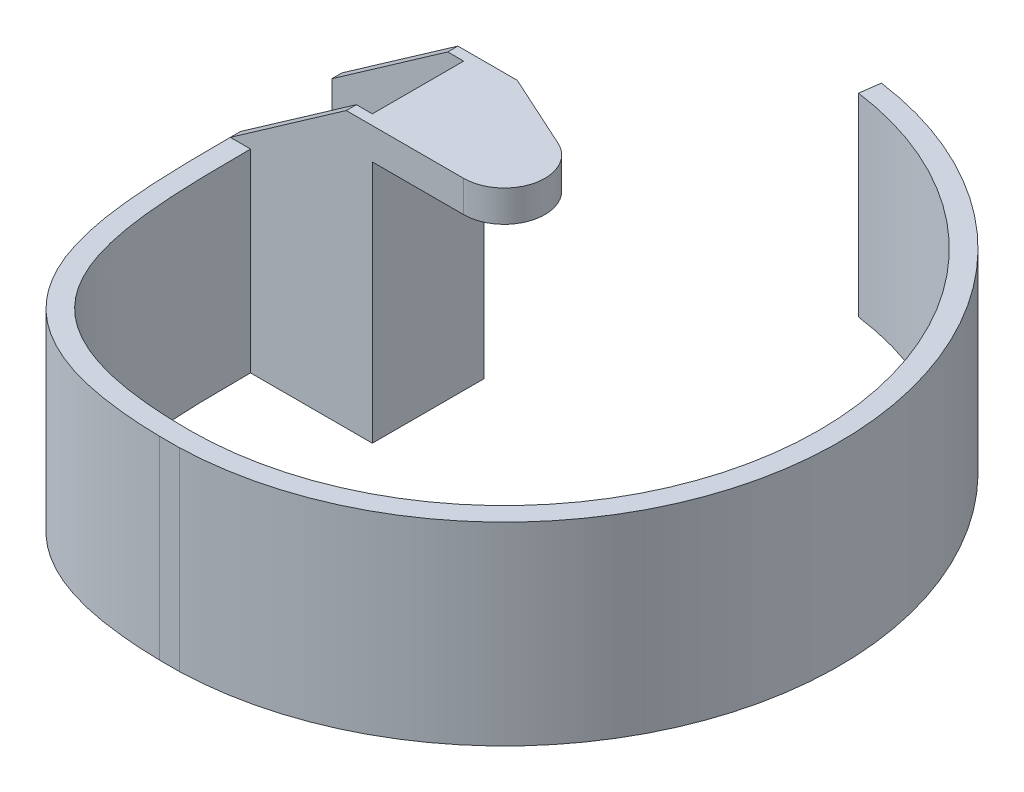
SolidWorks part; units mm, degrees
ref_plane "Front Plane" through (0, 0, 0) normal (0, 0, 1) x (1, 0, 0)
ref_plane "Top Plane" through (0, 0, 0) normal (0, 1, 0) x (1, 0, 0)
ref_plane "Right Plane" through (0, 0, 0) normal (1, 0, 0) x (0, 0, -1)
sketch "Agitator / Kick Alignment" plane through (0, 0, 0) normal (0, 1, 0) x (1, 0, 0)
  line L0 (-131.2224, 60.1613) -> (-110.3231, 213.6853) construction
  line L1 (5.6533, 41.527) -> (26.5533, 195.0509) construction
  line L2 (16.1033, 118.2889) -> (-271.78, 157.48) construction
  line L3 (-131.2224, 60.1613) -> (-110.3231, 213.6853)
  line L4 (5.6533, 41.527) -> (26.5533, 195.0509)
  line L5 (16.1033, 118.2889) -> (-271.78, 157.48)
sketch "Sketch3" plane through (0, 0, 0) normal (0, 1, 0) x (1, 0, 0)
  line L0 (5.6533, 41.527) -> (26.5533, 195.0509) construction
  line L1 (26.5533, 195.0509) -> (28.2664, 207.6348)
  line L2 (-133.35, -25.4) -> (0, -25.4)
  line L4 (-36.2865, 44.45) -> (-146.0084, 44.45)
  line L6 (-36.2865, 44.45) -> (10.5332, 23.113)
  line L7 (-6.3292, -209.4544) -> (6.3292, -209.4544)
  line L8 (128.5561, -196.85) -> (-132.7269, -196.85) construction
  line L9 (-146.0084, -25.4) -> (-146.0084, 44.45)
  line L10 (-133.35, -99.724) -> (-133.35, 83.6944) construction
  line L11 (-133.35, -25.4) -> (-133.35, 44.45)
  line L12 (-6.3292, -209.4544) -> (-6.3292, -209.4544)
  line L13 (-146.0084, -12.7416) -> (0, -12.7416) construction
  line L14 (-39.0349, 31.7916) -> (5.2839, 11.5944) construction
  line L15 (-39.0349, 31.7916) -> (-146.0084, 31.7916) construction
  line L16 (-133.35, -25.4) -> (-146.0084, -25.4)
  arc A0 (26.5533, 195.0509) -> (0, -196.85) centre (0, 0) cw
  arc A1 (28.2664, 207.6348) -> (6.3292, -209.4544) centre (0, 0) cw
  arc A4 (0, -25.4) -> (10.5332, 23.113) centre (0, 0) ccw
  arc A5 (0, -196.85) -> (-133.35, -25.4) centre (-91.3959, -130.3524) cw construction
  arc A6 (6.3292, -209.4544) -> (-138.0641, -13.6073) centre (-91.3959, -130.3524) cw construction
  arc A10 (-6.3292, -209.4544) -> (-6.3292, -209.4544) centre (-6.3292, -209.4544) cw
  arc A11 (-6.3292, -209.4544) -> (-6.3292, -209.4544) centre (-6.3292, -209.4544) ccw
  arc A12 (0, -12.7416) -> (5.2839, 11.5944) centre (0, 0) ccw construction
  spline S0 degree 1 poles (-146.0084, -12.7416) (-6.3292, -209.4544) knots 0 0 1 1 construction
  spline S1 degree 3 poles (-146.0084, -12.7416) (-146.0084, -14.4342) (-146.0083, -17.8078) (-146.0086, -21.6028) (-146.0083, -24.5474) (-146.0089, -27.9687) (-145.9928, -37.6758) (-145.8479, -52.8132) (-145.2521, -71.5713) (-144.0488, -89.4194) (-142.0319, -106.3622) (-137.955, -127.7287) (-131.2897, -147.2622) (-120.9286, -164.5766) (-111.1011, -176.2073) (-99.1376, -186.2307) (-85.0632, -194.4723) (-71.5911, -199.824) (-59.7326, -203.2181) (-50.2806, -205.3279) (-40.2501, -207.0086) (-31.3897, -208.0563) (-23.9871, -208.6846) (-18.276, -209.0513) (-13.3774, -209.2699) (-9.3819, -209.3926) (-7.3435, -209.4368) (-6.3292, -209.4544) knots -0.039869 -0.039869 -0.039869 -0.039869 -0.023876 -0.007997 -0.003998 0.003998 0.024105 0.088079 0.152052 0.216026 0.28 0.343974 0.471922 0.535895 0.599869 0.663843 0.727817 0.791791 0.823778 0.855765 0.887751 0.919738 0.935732 0.951725 0.967719 0.975715 0.983712 0.983712 0.983712 0.983712 only from (-146.0084, -25.4) to (-6.3292, -209.4544)
  spline S3 degree 3 poles (-133.35, -25.4) (-133.35, -131.2333) (-127, -196.85) (0, -196.85) knots 0 0 0 0 1 1 1 1
  point P22 (0, -209.4544)
  dimension "D1" = 196.85
  dimension "D6" = 25.4
  dimension "D9" = 317.5
  dimension "D10" = 381
  dimension "D3" = 12.7
  dimension "D4" = 69.85
  dimension "D7" = 24.5
  dimension "D8" = 133.35
extrude "Base extrude" add sketch "Sketch3" along normal blind 121.285 contours S3 L2 A4 L6 L4 L9 S1 L7 A1 L1 A0 region at (32.8405, 0, -200.6035)
extrude "Motor box & Core support" add sketch "Sketch3<4>" along normal offset from surface (172.085 mm away) 50.8 contours L16 L11 L4 L9 | L2 A4 L6 L4 L11 region at (-60.4233, 0, -7.6989) region at (-139.6792, 0, -9.525) up to face at (2.0047, 121.285, 15.5178) offset beyond the face yes
sketch "Sketch3<4>" plane through (0, 0, 0) normal (0, 1, 0) x (1, 0, 0) same geometry as "Sketch3"
sketch "Sketch4" plane through (0, 0, 25.4) normal (0, 0, 1) x (1, 0, 0)
  line L0 (25.4, 0) -> (25.4, 172.085) construction
  line L1 (25.4, 0) -> (-57.15, 0)
  line L2 (25.4, 0) -> (25.4, 152.4)
  line L3 (25.4, 152.4) -> (-57.15, 152.4)
  line L4 (-57.15, 0) -> (-57.15, 152.4)
  dimension "D1" = 152.4
  dimension "D2" = 82.55
extrude "Wheel space" cut sketch "Sketch4" against normal up to next
sketch "Sketch5" plane through (0, 172.085, 0) normal (0, 1, 0) x (1, 0, 0)
  line L0 (-146.0084, -25.4) -> (-146.0084, 44.45) construction
  line L7 (-63.5, 44.45) -> (-63.5, -25.4)
  line L8 (-63.5, 38.1) -> (-63.5, -19.05)
  line L18 (-146.0084, 38.1) -> (-146.0084, -19.05)
  line L22 (-139.6584, -19.05) -> (0, -19.05)
  line L23 (7.8999, 17.3348) -> (-37.6652, 38.1)
  line L24 (-37.6652, 38.1) -> (-139.6584, 38.1)
  line L25 (-139.6584, 38.1) -> (-139.6584, -19.05)
  line L26 (-146.0084, -19.05) -> (-63.5, -19.05)
  line L28 (-63.5, 38.1) -> (-146.0084, 38.1)
  arc A4 (0, -19.05) -> (7.8999, 17.3348) centre (0, 0) ccw
  dimension "D1" = 6.35
  dimension "D2" = 6.35
extrude "Motor space" cut sketch "Sketch5" against normal offset from surface (121.285 mm away) 50.8 up to face at (-24.6276, 0, 4.5125)
sketch "Sketch6" plane through (0, 0, 25.4) normal (0, 0, 1) x (1, 0, 0)
  line L0 (-146.0084, 121.285) -> (-73.4585, 172.085)
  line L1 (0, 172.085) -> (-146.0084, 172.085) construction
  line L2 (-73.4585, 172.085) -> (-146.0084, 172.085)
  line L3 (-146.0084, 172.085) -> (-146.0084, 121.285)
  dimension "D1" = 35
extrude "Motor Space Ribs" cut sketch "Sketch6" against normal through all
sketch "Sketch7" plane through (0, 172.085, 0) normal (0, 1, 0) x (1, 0, 0)
  circle A0 centre (0, 0) radius 7.62
  circle A1 centre (0, 0) radius 14.2875
  circle A2 centre (0, 0) radius 15.5702
  dimension "D1" = 15.24
  dimension "D2" = 28.575
  dimension "D3" = 31.1404
